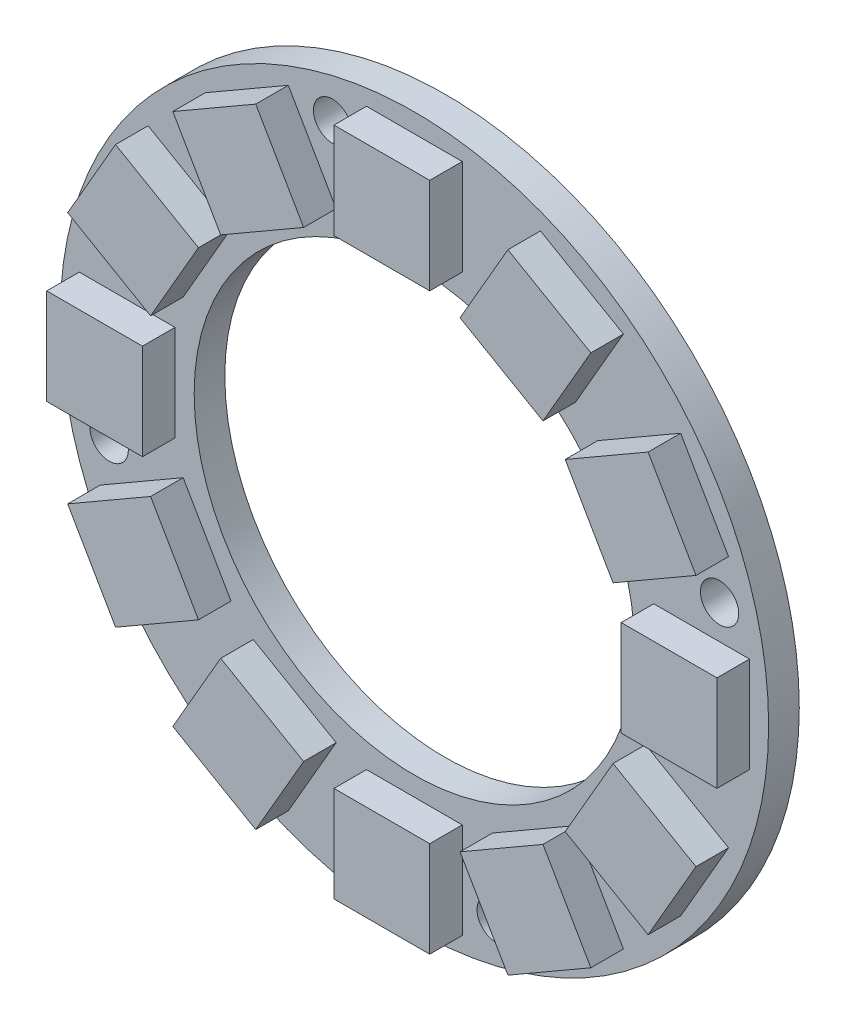
SolidWorks part; units mm, degrees
ref_plane "Front Plane" through (0, 0, 0) normal (0, 0, 1) x (1, 0, 0)
ref_plane "Top Plane" through (0, 0, 0) normal (0, 1, 0) x (1, 0, 0)
ref_plane "Right Plane" through (0, 0, 0) normal (1, 0, 0) x (0, 0, -1)
sketch "Sketch1" plane through (0, 0, 0) normal (0, 0, 1) x (1, 0, 0)
  circle A0 centre (0, 0) radius 11.5
  circle A1 centre (0, 0) radius 18.5
  dimension "D1" = 23
  dimension "D2" = 37
extrude "Boss-Extrude1" add sketch "Sketch1" along normal blind 1.6
sketch "Sketch2" plane through (0, 0, 1.6) normal (0, 0, 1) x (1, 0, 0)
  line L1 (-2.5, 17.5) -> (2.5, 17.5)
  line L2 (-2.5, 17.5) -> (-2.5, 12.5)
  line L3 (-2.5, 12.5) -> (2.5, 12.5)
  line L4 (2.5, 17.5) -> (2.5, 12.5)
  point P4 (0, 12.5)
  point P5 (-2.5, 15)
  dimension "D1" = 5
  dimension "D2" = 5
  dimension "D3" = 15
extrude "Boss-Extrude2" add sketch "Sketch2" along normal blind 1.7
ref_axis "Axis1" through (0, 0, 1.6) along (0, 0, -1)
pattern_circular "CirPattern1" count 12 over 360 about axis through (0, 0, 1.6) along (0, 0, -1) of "Boss-Extrude2"
sketch "Sketch3" plane through (0, 0, 1.6) normal (0, 0, 1) x (1, 0, 0)
  circle A0 centre (-4.2705, 15.9378) radius 1
  point P9 (-4.0068, 16.0061)
  dimension "D1" = 16.5
  dimension "D2" = 2
  dimension "D3" = 2.3612
extrude "Cut-Extrude1" cut sketch "Sketch3" against normal blind 2
pattern_circular "CirPattern2" count 4 over 360 about axis through (0, 0, 1.6) along (0, 0, -1) of "Cut-Extrude1"
